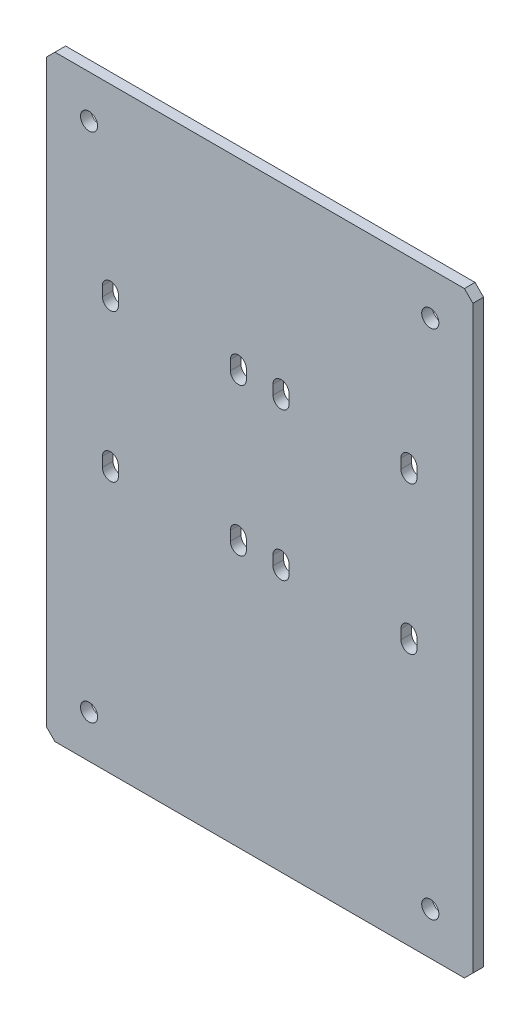
SolidWorks part; units mm, degrees
material "Acrylic (Medium-high impact)"
ref_plane "Front" through (0, 0, 0) normal (0, 0, 1) x (1, 0, 0)
ref_plane "Top" through (0, 0, 0) normal (0, 1, 0) x (1, 0, 0)
ref_plane "Right" through (0, 0, 0) normal (1, 0, 0) x (0, 0, -1)
sketch "Sketch1" plane through (0, 0, 0) normal (0, 0, 1) x (1, 0, 0)
  line L1 (0, 0) -> (127, 0)
  line L2 (0, 0) -> (0, 177.8)
  line L3 (0, 177.8) -> (127, 177.8)
  line L4 (127, 0) -> (127, 177.8)
extrude "Boss-Extrude1" add sketch "Sketch1" against normal blind 3.175
sketch "Sketch2" plane through (0, 0, 0) normal (0, 0, 1) x (1, 0, 0)
  line L0 (19.05, 121.7875) -> (19.05, 124.645) construction
  line L1 (16.6688, 121.7875) -> (16.6688, 124.645)
  line L2 (21.4312, 121.7875) -> (21.4312, 124.645)
  line L3 (19.05, 77.7875) -> (19.05, 80.645) construction
  line L4 (16.6688, 77.7875) -> (16.6688, 80.645)
  line L5 (21.4312, 77.7875) -> (21.4312, 80.645)
  line L6 (57.15, 124.645) -> (57.15, 121.7875) construction
  line L7 (59.5312, 124.645) -> (59.5312, 121.7875)
  line L8 (54.7688, 124.645) -> (54.7688, 121.7875)
  line L9 (57.15, 80.645) -> (57.15, 77.7875) construction
  line L10 (59.5312, 80.645) -> (59.5312, 77.7875)
  line L11 (54.7688, 80.645) -> (54.7688, 77.7875)
  line L12 (63.5, 0) -> (63.5, 21.0033) construction
  line L13 (0, 0) -> (127, 0) construction
  line L14 (107.95, 121.7875) -> (107.95, 124.645) construction
  line L15 (110.3312, 121.7875) -> (110.3312, 124.645)
  line L16 (105.5688, 121.7875) -> (105.5688, 124.645)
  line L17 (107.95, 77.7875) -> (107.95, 80.645) construction
  line L18 (110.3312, 77.7875) -> (110.3312, 80.645)
  line L19 (105.5688, 77.7875) -> (105.5688, 80.645)
  line L20 (69.85, 124.645) -> (69.85, 121.7875) construction
  line L21 (67.4688, 124.645) -> (67.4688, 121.7875)
  line L22 (72.2312, 124.645) -> (72.2312, 121.7875)
  line L23 (69.85, 80.645) -> (69.85, 77.7875) construction
  line L24 (67.4688, 80.645) -> (67.4688, 77.7875)
  line L25 (72.2312, 80.645) -> (72.2313, 77.7875)
  arc A0 (16.6688, 121.7875) -> (21.4312, 121.7875) centre (19.05, 121.7875) ccw
  arc A1 (21.4312, 124.645) -> (16.6688, 124.645) centre (19.05, 124.645) ccw
  arc A2 (16.6688, 77.7875) -> (21.4312, 77.7875) centre (19.05, 77.7875) ccw
  arc A3 (21.4312, 80.645) -> (16.6688, 80.645) centre (19.05, 80.645) ccw
  arc A4 (59.5312, 124.645) -> (54.7688, 124.645) centre (57.15, 124.645) ccw
  arc A5 (54.7688, 121.7875) -> (59.5312, 121.7875) centre (57.15, 121.7875) ccw
  arc A6 (59.5312, 80.645) -> (54.7688, 80.645) centre (57.15, 80.645) ccw
  arc A7 (54.7688, 77.7875) -> (59.5312, 77.7875) centre (57.15, 77.7875) ccw
  arc A8 (110.3312, 121.7875) -> (105.5688, 121.7875) centre (107.95, 121.7875) cw
  arc A9 (105.5688, 124.645) -> (110.3312, 124.645) centre (107.95, 124.645) cw
  arc A10 (110.3312, 77.7875) -> (105.5688, 77.7875) centre (107.95, 77.7875) cw
  arc A11 (105.5688, 80.645) -> (110.3312, 80.645) centre (107.95, 80.645) cw
  arc A12 (67.4688, 124.645) -> (72.2312, 124.645) centre (69.85, 124.645) cw
  arc A13 (72.2312, 121.7875) -> (67.4688, 121.7875) centre (69.85, 121.7875) cw
  arc A14 (67.4688, 80.645) -> (72.2312, 80.645) centre (69.85, 80.645) cw
  arc A15 (72.2313, 77.7875) -> (67.4688, 77.7875) centre (69.85, 77.7875) cw
  point P2 (19.05, 123.2163)
  point P9 (19.05, 79.2163)
  point P16 (57.15, 123.2163)
  point P21 (57.15, 79.2163)
  point P34 (107.95, 123.2163)
  point P41 (107.95, 79.2163)
  point P48 (69.85, 123.2163)
  point P55 (69.85, 79.2163)
  dimension "D2" = 7.62
  dimension "D4" = 12.7
  dimension "D5" = 44
  dimension "D6" = 77.7875
  dimension "D1" = 4.7625
  dimension "D3" = 38.1
extrude "Cut-Extrude1" cut sketch "Sketch2" against normal through all
sketch "Sketch5" plane through (0, 0, 0) normal (0, 0, 1) x (1, 0, 0)
  line L0 (0, 0) -> (127, 0) construction
  line L1 (0, 177.8) -> (0, 0) construction
  line L2 (127, 177.8) -> (0, 177.8) construction
  line L3 (127, 0) -> (127, 177.8) construction
  point P0 (12.7, 12.7)
  point P2 (12.7, 165.1)
  point P4 (114.3, 165.1)
  point P6 (114.3, 12.7)
  dimension "D1" = 12.7
  dimension "D2" = 12.7
  dimension "D3" = 12.7
  dimension "D4" = 12.7
hole_wizard "#10 Clearance Hole1" positions "Sketch5" profile "Sketch4" hole size "#10" standard "ANSI Inch" end condition through all
sketch "Sketch4" plane through (12.7, 12.7, 0) normal (1, 0, 0) x (0, -1, 0)
  line L0 (0, 0) -> (0, 3.175)
  line L1 (0, 3.175) -> (2.5527, 3.175)
  line L2 (2.5527, 3.175) -> (2.5527, 0)
  line L5 (2.5527, 0) -> (0, 0)
  line L11 (0, -6.35) -> (0, 107.95) construction
  dimension "Thru Hole Dia." = 5.1054
  dimension "Thru Hole Depth" = 3.175
chamfer "Chamfer1" distance 2.54 angle 45 4 edges at (0, 0, -1.5875) (127, 0, -1.5875) (127, 177.8, -1.5875) (0, 177.8, -1.5875)
